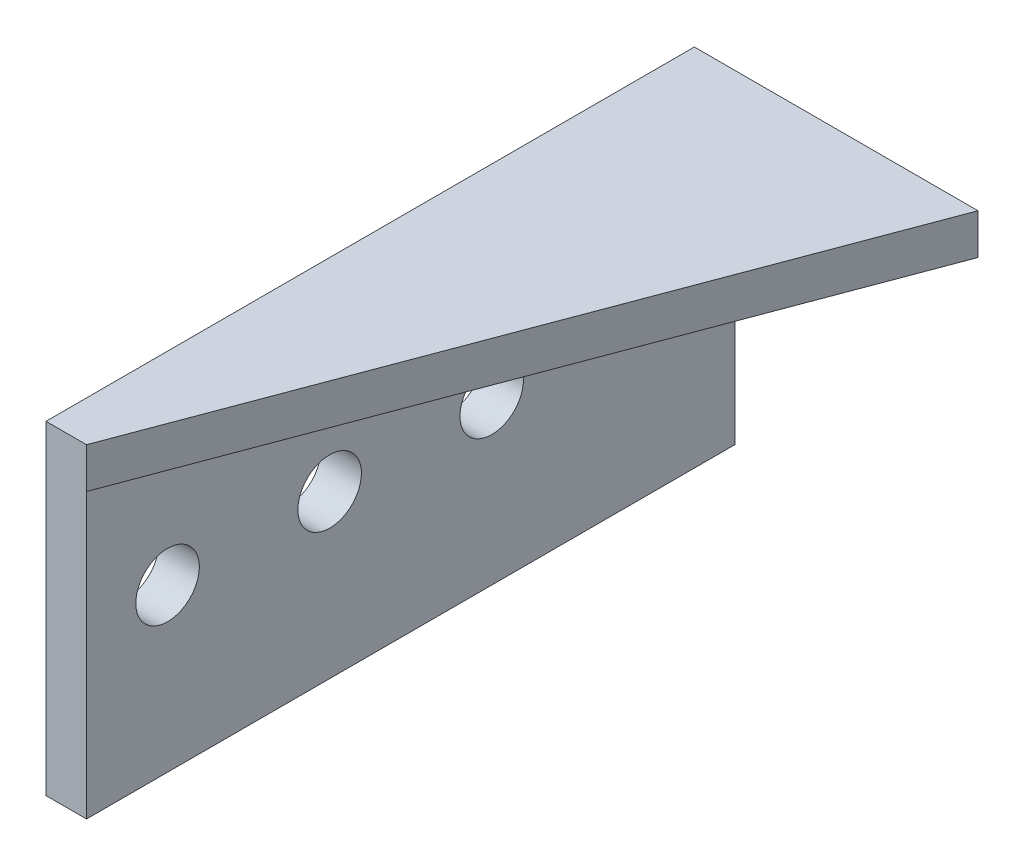
SolidWorks part; units mm, degrees
ref_plane "Front Plane" through (0, 0, 0) normal (0, 0, 1) x (1, 0, 0)
ref_plane "Top Plane" through (0, 0, 0) normal (0, 1, 0) x (1, 0, 0)
ref_plane "Right Plane" through (0, 0, 0) normal (1, 0, 0) x (0, 0, -1)
sketch "Sketch2" plane through (0, 0, 0) normal (0, 0, 1) x (1, 0, 0)
  line L0 (0, 0) -> (0, -25.4)
  line L1 (0, -25.4) -> (3.175, -25.4)
  line L2 (3.175, -25.4) -> (3.175, -3.175)
  line L3 (3.175, -3.175) -> (25.4, -3.175)
  line L4 (25.4, -3.175) -> (25.4, 0)
  line L5 (25.4, 0) -> (0, 0)
  dimension "D1" = 3.175
  dimension "D2" = 25.4
  dimension "D3" = 25.4
extrude "Boss-Extrude1" add sketch "Sketch2" along normal blind 50.8
sketch "Sketch5" plane through (3.175, 0, 0) normal (1, 0, 0) x (0, 0, -1)
  line L0 (-50.8, -25.4) -> (0, -25.4) construction
  line L1 (0, -25.4) -> (0, -3.175) construction
  circle A1 centre (-6.35, -12.7) radius 2.4892
  circle A2 centre (-19.05, -12.7) radius 2.4892
  circle A3 centre (-31.75, -12.7) radius 2.4892
  circle A4 centre (-44.45, -12.7) radius 2.4892
  dimension "D1" = 4.9784
  dimension "D2" = 12.7
  dimension "D3" = 6.35
  dimension "D4" = 4
  dimension "D5" = 12.7
extrude "Cut-Extrude1" cut sketch "Sketch5" against normal through all
sketch "Sketch6" plane through (0, -3.175, 0) normal (0, -1, 0) x (1, 0, 0)
  line L4 (3.175, 0) -> (25.4, 0) construction
  line L5 (25.4, 50.8) -> (25.4, 0) construction
  line L6 (25.4, 0) -> (25.4, 50.8)
  line L10 (3.175, 50.8) -> (22.225, 0)
  line L11 (3.175, 50.8) -> (25.4, 50.8)
  line L12 (22.225, 0) -> (25.4, 0)
  dimension "D1" = 3.175
extrude "Cut-Extrude2" cut sketch "Sketch6" against normal through all
